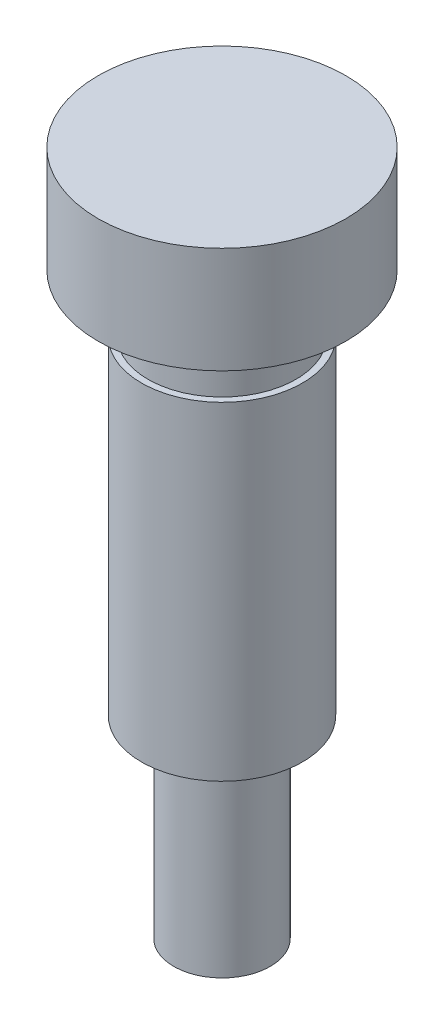
SolidWorks part; units mm, degrees
ref_plane "Front Plane" through (0, 0, 0) normal (0, 0, 1) x (1, 0, 0)
ref_plane "Top Plane" through (0, 0, 0) normal (0, 1, 0) x (1, 0, 0)
ref_plane "Right Plane" through (0, 0, 0) normal (1, 0, 0) x (0, 0, -1)
sketch "Sketch1" plane through (0, 0, 0) normal (0, 0, 1) x (1, 0, 0)
  line L0 (0, 0) -> (1.5, 0)
  line L1 (1.5, 0) -> (1.5, 6)
  line L2 (1.5, 6) -> (2.5, 6)
  line L3 (2.5, 6) -> (2.5, 16.2)
  line L4 (2.3, 16.2) -> (2.3, 18)
  line L5 (2.3, 18) -> (3.85, 18)
  line L6 (3.85, 18) -> (3.85, 21.3)
  line L7 (3.85, 21.3) -> (0, 21.3)
  line L8 (0, 21.3) -> (0, 0)
  line L9 (2.3, 16.2) -> (2.5, 16.2)
  dimension "D1" = 6
  dimension "D2" = 12
  dimension "D3" = 1.8
  dimension "D4" = 1.5
  dimension "D5" = 2.5
  dimension "D6" = 2.3
  dimension "D7" = 3.85
  dimension "D8" = 3.3
revolve "Revolve1" add sketch "Sketch1" angle 360 about L8
